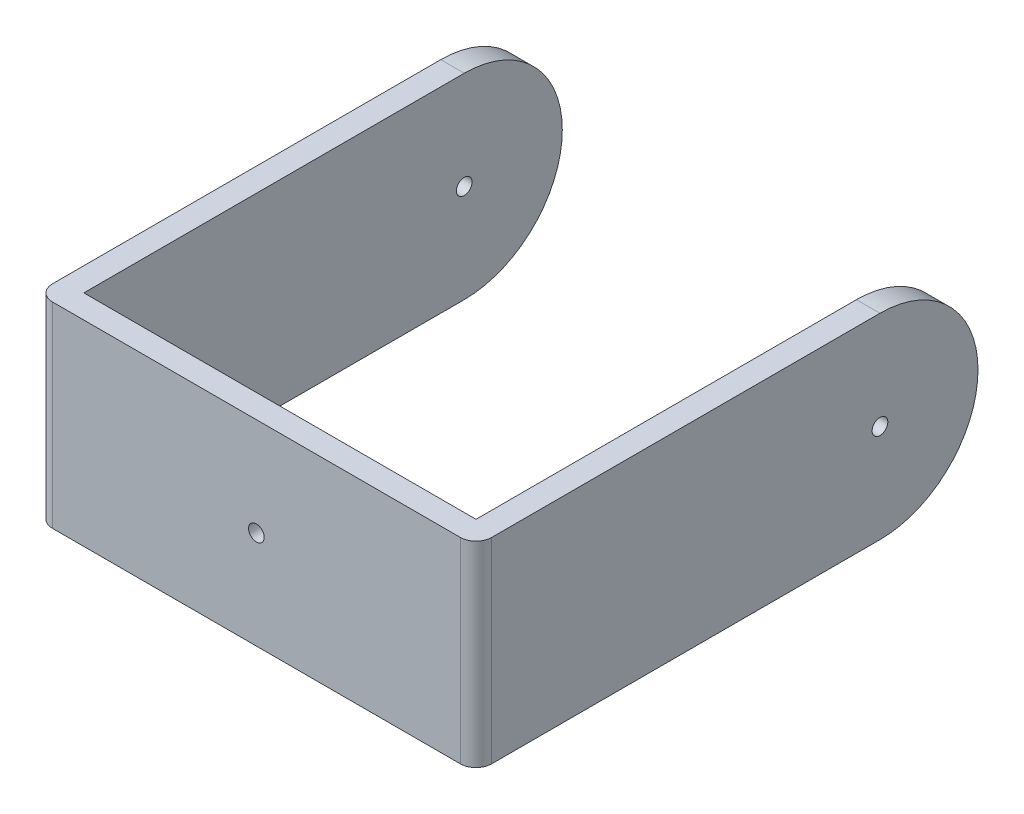
SolidWorks part; units mm, degrees
ref_plane "Front Plane" through (0, 0, 0) normal (0, 0, 1) x (1, 0, 0)
ref_plane "Top Plane" through (0, 0, 0) normal (0, 1, 0) x (1, 0, 0)
ref_plane "Right Plane" through (0, 0, 0) normal (1, 0, 0) x (0, 0, -1)
sketch "Sketch1" plane through (0, 0, 0) normal (0, 1, 0) x (1, 0, 0)
  line L0 (0, 0) -> (0, -62)
  line L1 (2, -64) -> (54, -64)
  line L2 (56, -62) -> (56, 0)
  line L3 (56, 0) -> (53, 0)
  line L4 (53, 0) -> (53, -61)
  line L5 (53, -61) -> (3, -61)
  line L6 (3, -61) -> (3, 0)
  line L7 (3, 0) -> (0, 0)
  arc A0 (54, -64) -> (56, -62) centre (54, -62) ccw
  arc A1 (2, -64) -> (0, -62) centre (2, -62) cw
  dimension "D1" = 2
extrude "Boss-Extrude1" add sketch "Sketch1" along normal blind 25
fillet "Fillet1" 2 edges at (1.5, 25, 0) (1.5, 0, 0) type full round first side face at (28, 25, 37.4828) second side face at (28, 0, 37.4828) middle face at (1.5, 12.5, 0)
fillet "Fillet2" 2 edges at (54.5, 25, 0) (54.5, 0, 0) type full round first side face at (28, 25, 39.9828) second side face at (28, 0, 39.9828) middle face at (54.5, 12.5, 0)
sketch "Sketch3" plane through (0, 0, 0) normal (-1, 0, 0) x (0, 0, 1)
  line L0 (12.5, 25) -> (12.5, 0)
  circle A0 centre (12.5, 12.5) radius 1
extrude "Cut-Extrude1" cut sketch "Sketch3" against normal through all contours L0 A0 | L0 A0 region at (0, 12.5, 12.9244) region at (0, 12.5, 12.0756)
sketch "Sketch4" plane through (0, 0, 64) normal (0, 0, 1) x (1, 0, 0)
  line L0 (2, 12.5) -> (54, 12.5)
  line L1 (2, 25) -> (2, 0) construction
  line L2 (54, 25) -> (54, 0) construction
  circle A0 centre (28, 12.5) radius 1
extrude "Cut-Extrude2" cut sketch "Sketch4" against normal up to next contours L0 A0 | L0 A0 region at (28, 12.9244, 64) region at (28, 12.0756, 64)
